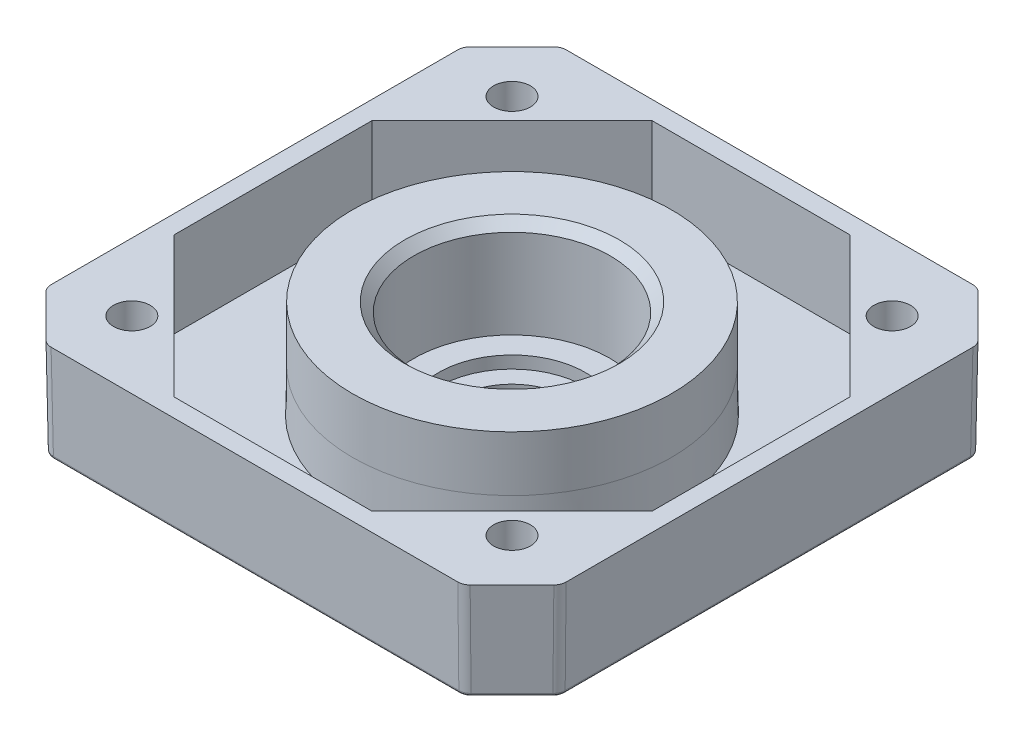
SolidWorks part; units mm, degrees
ref_plane "Front Plane" through (0, 0, 0) normal (0, 0, 1) x (1, 0, 0)
ref_plane "Top Plane" through (0, 0, 0) normal (0, 1, 0) x (1, 0, 0)
ref_plane "Right Plane" through (0, 0, 0) normal (1, 0, 0) x (0, 0, -1)
sketch "Sketch1" plane through (0, 0, 0) normal (0, 1, 0) x (1, 0, 0)
  line L0 (-17, 21) -> (-21, 17)
  line L1 (-17, 21) -> (17, 21)
  line L2 (-21, 17) -> (-21, -17)
  line L3 (-17, -21) -> (17, -21)
  line L4 (21, 17) -> (21, -17)
  line L5 (-21, -17) -> (-17, -21)
  line L6 (17, -21) -> (21, -17)
  line L7 (17, 21) -> (21, 17)
  point P1 (0, 21)
  point P2 (21, 0)
  dimension "D1" = 42
  dimension "D2" = 4
extrude "Boss-Extrude1" add sketch "Sketch1" against normal blind 8 draft 1
sketch "Sketch14" plane through (0, -8, 0) normal (0, -1, 0) x (1, 0, 0)
  circle A0 centre (0, 0) radius 11
  dimension "D1" = 22
extrude "Boss-Extrude8" add sketch "Sketch14" along normal blind 2
fillet "Fillet2" radius 1 8 edges at (-20.9302, -4, 16.9711) (-16.9711, -4, 20.9302) (16.9711, -4, 20.9302) (20.9302, -4, 16.9711) (-20.9302, -4, -16.9711) (-16.9711, -4, -20.9302) (20.9302, -4, -16.9711) (16.9711, -4, -20.9302)
sketch "Sketch2" plane through (0, 0, 0) normal (0, 1, 0) x (1, 0, 0)
  line L3 (-8.0772, 19.5) -> (-19.5, 8.0772)
  line L4 (-19.5, 8.0772) -> (-19.5, -8.0772)
  line L5 (-19.5, -8.0772) -> (-8.0772, -19.5)
  line L6 (-8.0772, -19.5) -> (8.0772, -19.5)
  line L7 (8.0772, -19.5) -> (19.5, -8.0772)
  line L8 (19.5, -8.0772) -> (19.5, 8.0772)
  line L9 (19.5, 8.0772) -> (8.0772, 19.5)
  line L10 (-19.5, 8.0772) -> (8.0772, -19.5) construction
  line L12 (-19.5, 0) -> (19.5, 0) construction
  line L39 (-8.0772, 19.5) -> (8.0772, 19.5)
  point P2 (0, 0)
  dimension "D3" = 39
extrude "Cut-Extrude1" cut sketch "Sketch2" against normal blind 7
sketch "Sketch6" plane through (0, -7, 0) normal (0, 1, 0) x (1, 0, 0)
  circle A0 centre (0, 0) radius 13
  dimension "D1" = 26
extrude "Boss-Extrude5" add sketch "Sketch6" against normal up to body draft 1 from offset 3.5 separate body draft outward yes
sketch "Sketch7" plane through (0, -3.5, 0) normal (0, 1, 0) x (1, 0, 0)
  circle A1 centre (0, 0) radius 13
  circle A2 centre (0, 0) radius 13
  dimension "D1" = 0
extrude "Boss-Extrude6" add sketch "Sketch7" along normal blind 4.5
sketch "Sketch9" plane through (0, 0, 0) normal (0, 0, 1) x (1, 0, 0)
  line L1 (13, 1) -> (-13, 1) construction
  line L2 (6, -7) -> (6, -8)
  line L3 (6, -8) -> (4.5, -8)
  line L4 (4.5, -8) -> (4.5, -9.5)
  line L5 (5, -10) -> (0, -10)
  line L7 (0, 1) -> (8.75, 1)
  line L9 (0, 1) -> (0, -10) construction
  line L10 (6, -7) -> (8, -7)
  line L11 (8, -7) -> (8, 0.25)
  line L12 (8, 0.25) -> (8.75, 1)
  line L13 (0, 1) -> (0, -10)
  line L14 (-11, -10) -> (11, -10) construction
  arc A0 (4.5, -9.5) -> (5, -10) centre (5, -9.5) ccw
  dimension "D8" = 0.5
  dimension "D1" = 9
  dimension "D2" = 12
  dimension "D3" = 16
  dimension "D4" = 135
  dimension "D5" = 0.75
  dimension "D6" = 8
  dimension "D7" = 9
revolve "Cut-Revolve1" cut sketch "Sketch9" angle 360 about L9
sketch "Sketch15" plane through (0, 0, 0) normal (0, 1, 0) x (1, 0, 0)
  line L0 (-15.5, -15.5) -> (-15.5, 15.5) construction
  line L1 (-15.5, 15.5) -> (15.5, 15.5) construction
  circle A0 centre (-15.5, 15.5) radius 1.5
  circle A1 centre (-15.5, -15.5) radius 1.5
  circle A2 centre (15.5, -15.5) radius 1.5
  circle A3 centre (15.5, 15.5) radius 1.5
  point P8 (0, 15.5)
  point P9 (-15.5, 0)
  dimension "D2" = 3
  dimension "D1" = 31
extrude "Cut-Extrude7" cut sketch "Sketch15" against normal through all
fillet "Fillet3" radius 0.25 2 edges at (0, -8, -11) (0, -10, -11)
fillet "Fillet4" radius 0.25 16 edges at (-20.7843, -8, -16.9106) (-18.9013, -8, -18.9013) (-16.9106, -8, -20.7843) (0, -8, -20.8604) (16.9106, -8, -20.7843) (18.9013, -8, -18.9013) (20.7843, -8, -16.9106) (20.8604, -8, 0) (20.7843, -8, 16.9106) (18.9013, -8, 18.9013) (16.9106, -8, 20.7843) (0, -8, 20.8604) (-16.9106, -8, 20.7843) (-18.9013, -8, 18.9013) (-20.7843, -8, 16.9106) (-20.8604, -8, 0)
